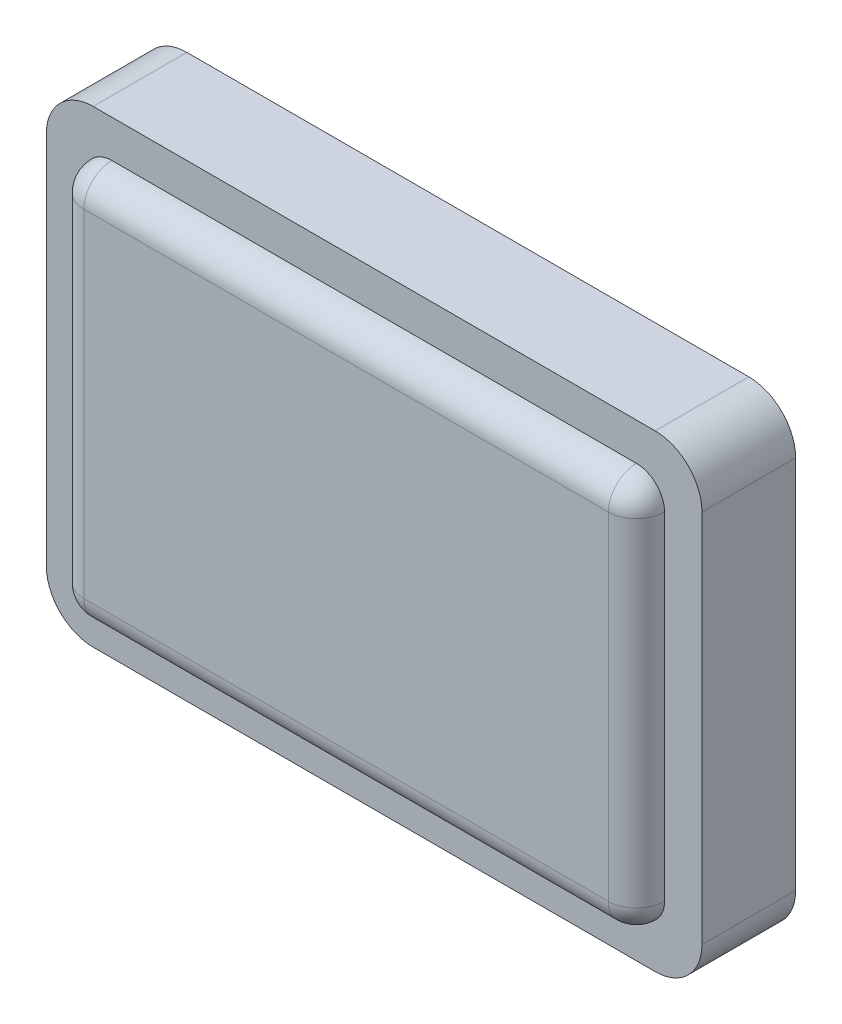
SolidWorks part; units mm, degrees
ref_plane "Спереди" through (0, 0, 0) normal (0, 0, 1) x (1, 0, 0)
ref_plane "Сверху" through (0, 0, 0) normal (0, 1, 0) x (1, 0, 0)
ref_plane "Справа" through (0, 0, 0) normal (1, 0, 0) x (0, 0, -1)
sketch "Эскиз1" plane through (0, 0, 0) normal (0, 0, 1) x (1, 0, 0)
  line L1 (-3.5, -2.5) -> (3.5, -2.5)
  line L2 (-3.5, -2.5) -> (-3.5, 2.5)
  line L3 (-3.5, 2.5) -> (3.5, 2.5)
  line L4 (3.5, -2.5) -> (3.5, 2.5)
  line L5 (-3.5, -2.5) -> (3.5, 2.5) construction
  line L6 (-3.5, 2.5) -> (3.5, -2.5) construction
  point P0 (0, 0)
  dimension "D1" = 7
  dimension "D2" = 5
extrude "Бобышка-Вытянуть1" add sketch "Эскиз1" along normal blind 1
fillet "Скругление1" radius 0.5 4 edges at (-3.5, -2.5, 0.5) (3.5, -2.5, 0.5) (-3.5, 2.5, 0.5) (3.5, 2.5, 0.5)
sketch "Эскиз2" plane through (0, 0, 1) normal (0, 0, 1) x (1, 0, 0)
  line L0 (3, 2.5) -> (-3, 2.5) construction
  line L1 (-3.1, 2.1) -> (3.1, 2.1)
  line L2 (-3.1, 2.1) -> (-3.1, -2.1)
  line L3 (-3.1, -2.1) -> (3.1, -2.1)
  line L4 (3.1, 2.1) -> (3.1, -2.1)
  line L5 (-3.1, 2.1) -> (3.1, -2.1) construction
  line L6 (-3.1, -2.1) -> (3.1, 2.1) construction
  line L7 (3.5, -2) -> (3.5, 2) construction
  point P0 (0, 0)
  dimension "D1" = 0.4
  dimension "D2" = 0.4
extrude "Бобышка-Вытянуть2" add sketch "Эскиз2" along normal blind 0.3
fillet "Скругление2" radius 0.3 4 edges at (0, -2.1, 1.3) (3.1, 0, 1.3) (0, 2.1, 1.3) (-3.1, 0, 1.3)
